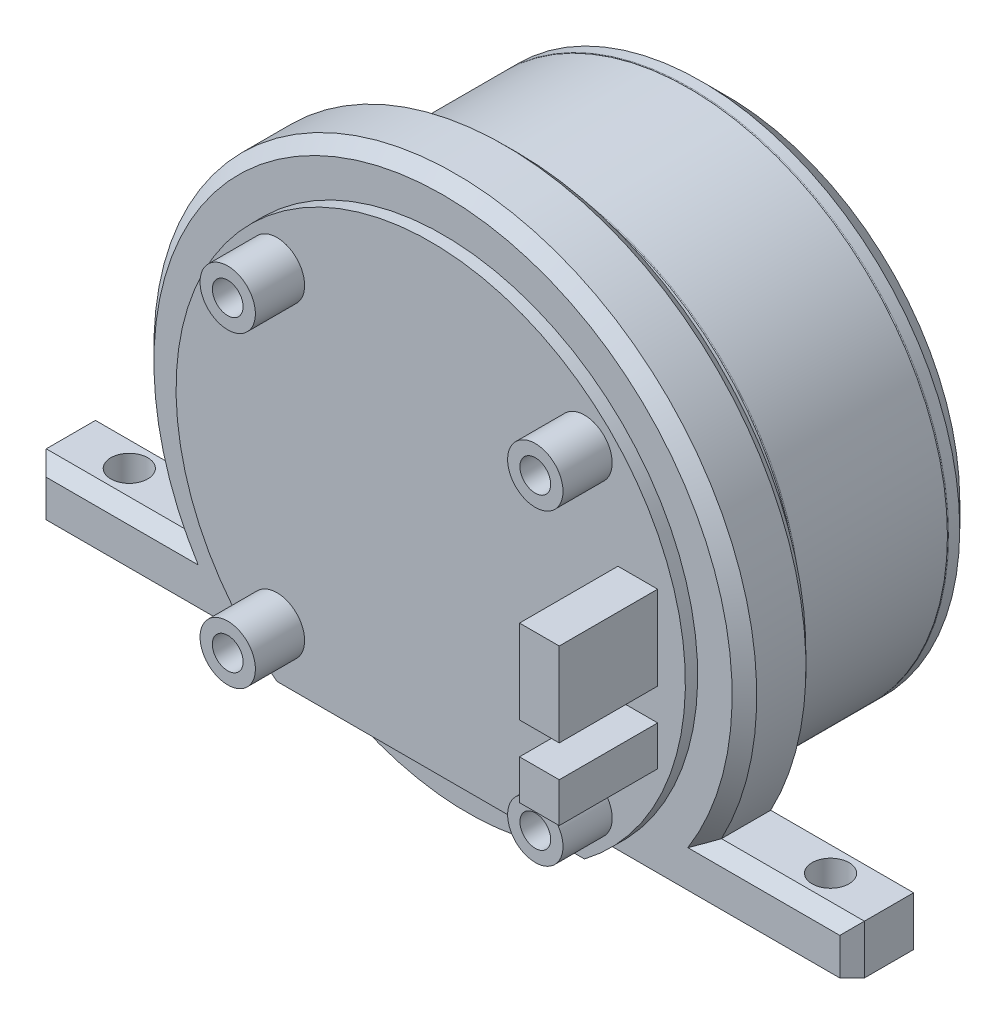
SolidWorks part; units mm, degrees
ref_plane "Front Plane" through (0, 0, 0) normal (0, 0, 1) x (1, 0, 0)
ref_plane "Top Plane" through (0, 0, 0) normal (0, 1, 0) x (1, 0, 0)
ref_plane "Right Plane" through (0, 0, 0) normal (1, 0, 0) x (0, 0, -1)
sketch "Sketch1" plane through (0, 0, 0) normal (0, 0, 1) x (1, 0, 0)
  circle A0 centre (0, 0) radius 21
  dimension "D1" = 42
extrude "Boss-Extrude1" add sketch "Sketch1" along normal blind 3
chamfer "Chamfer1" distance 2 angle 45 1 edges at (21, 0, 0)
fillet "Fillet1" radius 0.1 1 edges at (21, 0, 3)
sketch "Sketch2" plane through (0, 0, 3) normal (0, 0, 1) x (1, 0, 0)
  circle A0 centre (0, 0) radius 21 construction
  circle A1 centre (0, 0) radius 21
extrude "Boss-Extrude2" add sketch "Sketch2" along normal blind 12
fillet "Fillet2" radius 0.1 1 edges at (21, 0, 15)
sketch "Sketch3" plane through (0, 0, 15) normal (0, 0, 1) x (1, 0, 0)
  circle A0 centre (0, 0) radius 21 construction
  circle A1 centre (0, 0) radius 21
extrude "Boss-Extrude3" add sketch "Sketch3" along normal blind 6
sketch "Sketch4" plane through (0, 0, 0) normal (0, 0, -1) x (-1, 0, 0)
  line L0 (-10, 0) -> (0, 0) construction
  circle A0 centre (0, 0) radius 3
  circle A1 centre (-10, 0) radius 1.5
  circle A2 centre (0, 0) radius 3
  circle A3 centre (0, 10) radius 1.5
  circle A4 centre (0, 0) radius 3
  circle A5 centre (10, 0) radius 1.5
  circle A6 centre (0, 0) radius 3
  circle A7 centre (0, -10) radius 1.5
  point P17 (0, 0)
  dimension "D1" = 6
  dimension "D2" = 3
  dimension "D3" = 10
  dimension "D4" = 4
extrude "Cut-Extrude1" cut sketch "Sketch4" against normal blind 6 contours A0 | A1 | A3 | A5 | A7 region at (0, 0, 0) region at (10, 0, 0) region at (0, 10, 0) region at (-10, 0, 0) region at (0, -10, 0)
ref_plane "Plane1" through (0, 0, 17) normal (0, 0, 1) x (1, 0, 0)
sketch "Sketch5" plane through (0, 0, 17) normal (0, 0, 1) x (1, 0, 0)
  line L0 (21.6333, -11.5) -> (33.25, -11.5)
  line L1 (-33.25, -15.5) -> (33.25, -15.5)
  line L2 (-33.25, -15.5) -> (-33.25, -11.5)
  line L3 (-33.25, -11.5) -> (-21.6333, -11.5)
  line L4 (33.25, -15.5) -> (33.25, -11.5)
  line L5 (0, 0) -> (0, -15.5) construction
  arc A0 (21.6333, -11.5) -> (-21.6333, -11.5) centre (0, 0) ccw
  dimension "D1" = 49
  dimension "D2" = 66.5
  dimension "D3" = 4
  dimension "D4" = 15.5
extrude "Boss-Extrude4" add sketch "Sketch5" along normal blind 6
chamfer "Chamfer2" distance 1 angle 45 10 edges at (0, 24.5, 17) (0, 24.5, 23) (-33.25, -13.5, 17) (-27.4417, -11.5, 17) (33.25, -13.5, 17) (27.4417, -11.5, 17) (-33.25, -13.5, 23) (-27.4417, -11.5, 23) (33.25, -13.5, 23) (27.4417, -11.5, 23)
sketch "Sketch6" plane through (0, -11.5, 0) normal (0, 1, 0) x (1, 0, 0)
  line L0 (-28.5, -20) -> (28.5, -20) construction
  line L1 (0, -20) -> (0, 0) construction
  line L2 (19, 0) -> (-19, 0) construction
  line L3 (-23.5, -23) -> (23.5, -23) construction
  circle A0 centre (-28.5, -20) radius 1.5
  circle A1 centre (28.5, -20) radius 1.5
  dimension "D3" = 3
  dimension "D1" = 3
  dimension "D2" = 57
extrude "Cut-Extrude2" cut sketch "Sketch6" against normal through all and the other way through all
sketch "Sketch7" plane through (0, 0, 23) normal (0, 0, 1) x (1, 0, 0)
  line L0 (12.4996, -16.5) -> (-12.4996, -16.5)
  line L1 (-32.25, -15.5) -> (32.25, -15.5) construction
  arc A0 (12.4996, -16.5) -> (-12.4996, -16.5) centre (0, 0) ccw
  dimension "D2" = 20.7
  dimension "D1" = 1
extrude "Boss-Extrude5" add sketch "Sketch7" along normal blind 1
sketch "Sketch8" plane through (0, 0, 24) normal (0, 0, 1) x (1, 0, 0)
  line L1 (-12.5, 12.5) -> (12.5, 12.5) construction
  line L2 (-12.5, 12.5) -> (-12.5, -12.5) construction
  line L3 (-12.5, -12.5) -> (12.5, -12.5) construction
  line L4 (12.5, 12.5) -> (12.5, -12.5) construction
  line L5 (-12.5, 12.5) -> (12.5, -12.5) construction
  line L6 (-12.5, -12.5) -> (12.5, 12.5) construction
  circle A0 centre (-12.5, 12.5) radius 2.25
  circle A1 centre (12.5, 12.5) radius 2.25
  circle A2 centre (12.5, -12.5) radius 2.25
  circle A3 centre (-12.5, -12.5) radius 2.25
  point P0 (0, 0)
  dimension "D2" = 4.5
  dimension "D1" = 25
extrude "Boss-Extrude6" add sketch "Sketch8" along normal blind 4
sketch "Sketch9" plane through (0, 0, 28) normal (0, 0, 1) x (1, 0, 0)
  circle A2 centre (12.5, 12.5) radius 1.25
  circle A3 centre (12.5, 12.5) radius 1.25
  circle A4 centre (12.5, -12.5) radius 1.25
  circle A5 centre (12.5, -12.5) radius 1.25
  circle A8 centre (-12.5, 12.5) radius 1.25
  circle A9 centre (-12.5, 12.5) radius 1.25
  circle A11 centre (-12.5, -12.5) radius 1.25
  circle A12 centre (-12.5, -12.5) radius 1.25
  dimension "D1" = 1
  dimension "D2" = 1
  dimension "D3" = 1
  dimension "D4" = 1
extrude "Cut-Extrude3" cut sketch "Sketch9" against normal blind 4
sketch "Sketch10" plane through (0, 0, 24) normal (0, 0, 1) x (1, 0, 0)
  line L0 (15.2167, -1.355) -> (15.2167, -3.9466) construction
  line L1 (15.2167, 5.4678) -> (18.4459, 5.4678)
  line L2 (15.2167, 5.4678) -> (15.2167, -1.355)
  line L3 (15.2167, -1.355) -> (18.4459, -1.355)
  line L4 (18.4459, 5.4678) -> (18.4459, -1.355)
  line L5 (15.2167, -3.9466) -> (18.4459, -3.9466)
  line L6 (15.2167, -3.9466) -> (15.2167, -7.1758)
  line L7 (15.2167, -7.1758) -> (18.4459, -7.1758)
  line L8 (18.4459, -3.9466) -> (18.4459, -7.1758)
  line L9 (18.4459, -3.9466) -> (18.4459, -1.355) construction
  point P9 (14.7883, -1.5711)
  point P10 (12.5472, -1.6394)
extrude "Boss-Extrude7" add sketch "Sketch10" along normal blind 8
